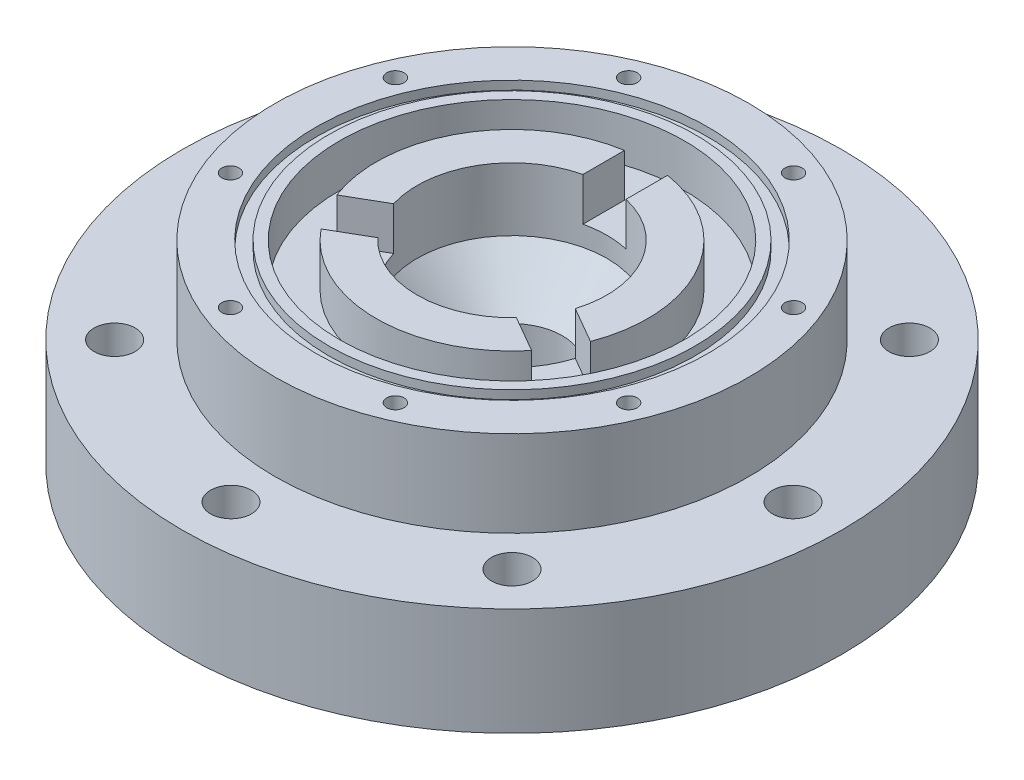
SolidWorks part; units mm, degrees
ref_plane "Front Plane" through (0, 0, 0) normal (0, 0, 1) x (1, 0, 0)
ref_plane "Top Plane" through (0, 0, 0) normal (0, 1, 0) x (1, 0, 0)
ref_plane "Right Plane" through (0, 0, 0) normal (1, 0, 0) x (0, 0, -1)
sketch "Sketch3" plane through (0, 0, 0) normal (1, 0, 0) x (0, 0, -1)
  line L2 (76.5, 15) -> (55, 15)
  line L3 (55, 15) -> (55, 35)
  line L4 (55, 35) -> (22.025, 35)
  line L7 (11.665, 0) -> (16.665, 0)
  line L8 (76.5, 15) -> (76.5, -10)
  line L9 (53.85, -10) -> (53.85, 86.2223) construction
  line L10 (76.5, -10) -> (53.85, -10)
  line L11 (11.665, 0) -> (11.665, 10)
  line L12 (11.665, 10) -> (22.025, 20.36)
  line L13 (22.025, 20.36) -> (22.025, 35)
  line L14 (0, 0) -> (0, 51.2471) construction
  line L15 (11.665, 10) -> (19.7366, 10) construction
  line L16 (65.2, -29.1535) -> (65.2, 61.9555) construction
  line L17 (0, 0) -> (11.665, 0) construction
  arc A3 (53.85, -10) -> (16.665, 0) centre (30.7197, -21.8739) ccw
  point P18 (35.2575, -5)
  dimension "D6" = 26
  dimension "D1" = 10
  dimension "D2" = 55
  dimension "D3" = 76.5
  dimension "D4" = 45
  dimension "D5" = 53.85
  dimension "D7" = 11.665
  dimension "D9" = 25
  dimension "D11" = 10
  dimension "D12" = 45
  dimension "D13" = 44.05
  dimension "D14" = 5
  dimension "D15" = 65.2
revolve "Revolve1" add sketch "Sketch3" angle 360 about L14
sketch "Sketch4" plane through (0, 0, 0) normal (0, 1, 0) x (1, 0, 0)
  line L0 (0, 0) -> (-65.2, 0) construction
  circle A0 centre (-65.2, 0) radius 4.7625
  dimension "D2" = 9.525
  dimension "D1" = 65.2
extrude "Cut-Extrude2" cut sketch "Sketch4" along normal through all both and the other way through all contours A0
pattern_circular "CirPattern1" count 8 over 360 about axis through (0, 0, 0) along (0, 1, 0) of "Cut-Extrude2" reverse direction yes
sketch "Sketch6" plane through (0, 35, 0) normal (0, 1, 0) x (1, 0, 0)
  circle A0 centre (0, 0) radius 31.5
  circle A1 centre (0, 0) radius 40
  point P19 (0, 0)
  dimension "D1" = 63
  dimension "D2" = 80
extrude "Cut-Extrude3" cut sketch "Sketch6" against normal blind 10
sketch "Sketch7" plane through (0, 35, 0) normal (0, 1, 0) x (1, 0, 0)
  line L0 (0, 0) -> (0, 31.5) construction
  line L1 (-5, 31.5) -> (5, 31.5)
  line L2 (5, 31.5) -> (5, 21.45)
  line L3 (5, 21.45) -> (-5, 21.45)
  line L4 (-5, 21.45) -> (-5, 31.5)
  circle A0 centre (0, 0) radius 31.5 construction
  circle A1 centre (0, 0) radius 22.025 construction
  point P8 (0, 31.5)
  dimension "D1" = 10
extrude "Cut-Extrude4" cut sketch "Sketch7" against normal blind 10
pattern_circular "CirPattern2" count 3 over 360 about axis through (0, 0, 0) along (0, 1, 0) of "Cut-Extrude4" reverse direction yes
sketch "Sketch9" plane through (0, 35, 0) normal (0, 1, 0) x (1, 0, 0)
  line L0 (0, 0) -> (46.194, 19.1342) construction
  line L1 (0, 0) -> (100.5921, 0) construction
  circle A0 centre (46.194, 19.1342) radius 2
  dimension "D2" = 4
  dimension "D1" = 50
  dimension "D3" = 22.5
extrude "Cut-Extrude5" cut sketch "Sketch9" against normal blind 10
pattern_circular "CirPattern3" count 8 over 360 about axis through (0, 0, 0) along (0, 1, 0) of "Cut-Extrude5" reverse direction yes
sketch "Sketch10" plane through (0, 35, 0) normal (0, 1, 0) x (1, 0, 0)
  circle A0 centre (0, 0) radius 42.5
  circle A1 centre (0, 0) radius 45.5
  dimension "D1" = 3
  dimension "D2" = 85
extrude "Cut-Extrude6" cut sketch "Sketch10" against normal blind 2
